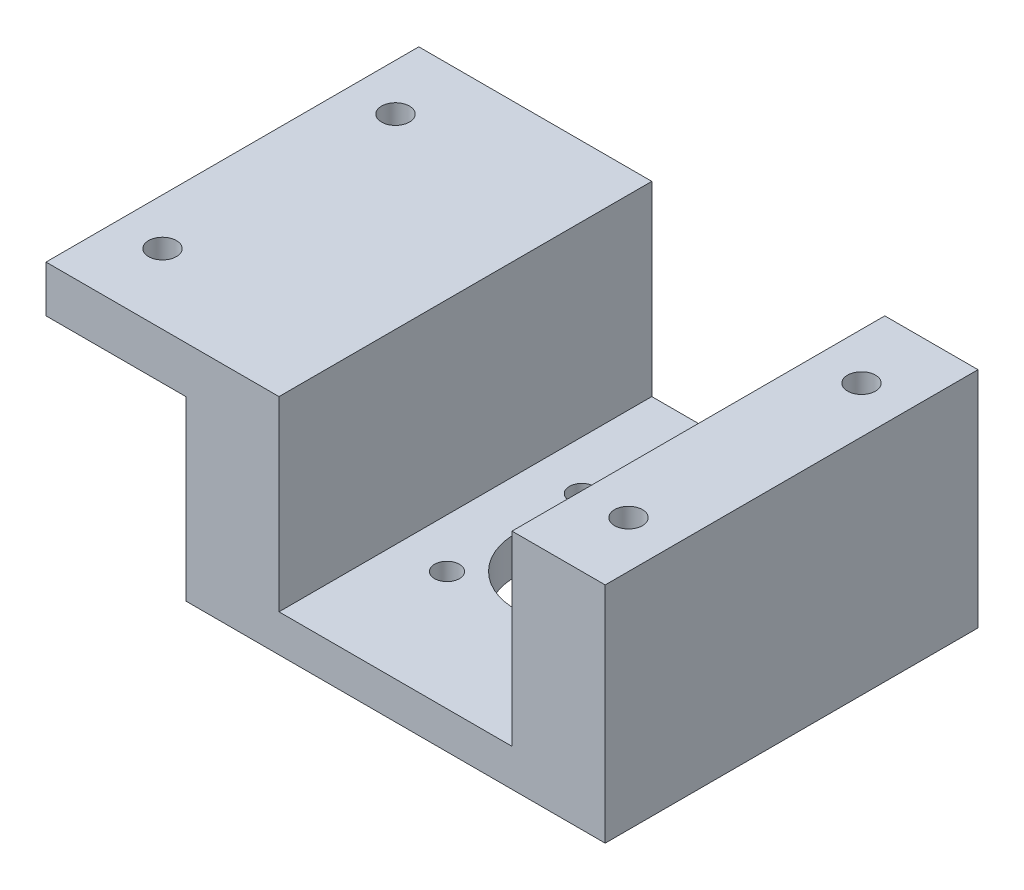
SolidWorks part; units mm, degrees
material "6061 Alloy"
ref_plane "Front Plane" through (0, 0, 0) normal (0, 0, 1) x (1, 0, 0)
ref_plane "Top Plane" through (0, 0, 0) normal (0, 1, 0) x (1, 0, 0)
ref_plane "Right Plane" through (0, 0, 0) normal (1, 0, 0) x (0, 0, -1)
sketch "Sketch1" plane through (0, 0, 0) normal (0, 1, 0) x (1, 0, 0)
  line L1 (-38.1, -25.4) -> (38.1, -25.4)
  line L2 (-38.1, -25.4) -> (-38.1, 25.4)
  line L3 (-38.1, 25.4) -> (38.1, 25.4)
  line L4 (38.1, -25.4) -> (38.1, 25.4)
  line L5 (-38.1, -25.4) -> (38.1, 25.4) construction
  line L6 (-38.1, 25.4) -> (38.1, -25.4) construction
  point P0 (0, 0)
  dimension "D1" = 76.2
  dimension "D2" = 50.8
extrude "Boss-Extrude1" add sketch "Sketch1" along normal blind 30.48
sketch "Sketch2" plane through (0, 0, 0) normal (0, -1, 0) x (1, 0, 0)
  line L0 (-38.1, 0) -> (38.1, 0) construction
  line L1 (-38.1, -25.4) -> (-38.1, 25.4) construction
  line L2 (38.1, 25.4) -> (38.1, -25.4) construction
  line L3 (0, 25.4) -> (0, -25.4) construction
  line L4 (-38.1, 25.4) -> (38.1, 25.4) construction
  line L5 (38.1, -25.4) -> (-38.1, -25.4) construction
  circle A1 centre (9.525, 0) radius 9
  point P12 (-9.525, 0)
  point P13 (9.525, 0)
  dimension "D3" = 18
  dimension "D1" = 19.05
  dimension "D2" = 9.525
extrude "Cut-Extrude1" cut sketch "Sketch2" against normal through all contours A1
sketch "Sketch3" plane through (0, 30.48, 0) normal (0, 1, 0) x (1, 0, 0)
  line L0 (9.525, 0) -> (-9.525, 0) construction
  line L1 (-12.7, -19.05) -> (12.7, -19.05)
  line L2 (-25.4, -6.35) -> (-25.4, 6.35)
  line L3 (-12.7, 19.05) -> (12.7, 19.05)
  line L4 (25.4, -6.35) -> (25.4, 6.35)
  line L5 (-25.4, -19.05) -> (25.4, 19.05) construction
  line L6 (-25.4, 19.05) -> (25.4, -19.05) construction
  arc A0 (12.7, 19.05) -> (25.4, 6.35) centre (12.7, 6.35) cw
  arc A1 (25.4, -6.35) -> (12.7, -19.05) centre (12.7, -6.35) cw
  arc A2 (-12.7, -19.05) -> (-25.4, -6.35) centre (-12.7, -6.35) cw
  arc A3 (-25.4, 6.35) -> (-12.7, 19.05) centre (-12.7, 6.35) cw
  point P0 (0, 0)
  point P9 (0, 0)
  point P22 (-21.87, 0)
  dimension "D3" = 12.7
  dimension "D1" = 38.1
  dimension "D2" = 50.8
  dimension "D4" = 19.05
extrude "Cut-Extrude2" cut sketch "Sketch3" against normal blind 25.4
sketch "Sketch4" plane through (0, 0, 0) normal (0, -1, 0) x (1, 0, 0)
  line L0 (-31.75, 25.4) -> (-31.75, -25.4) construction
  line L1 (-38.1, 25.4) -> (38.1, 25.4) construction
  line L2 (38.1, -25.4) -> (-38.1, -25.4) construction
  line L3 (31.75, 25.4) -> (31.75, -25.4) construction
  line L4 (-38.1, -25.4) -> (-38.1, 25.4) construction
  line L5 (38.1, 25.4) -> (38.1, -25.4) construction
  line L6 (-31.75, 0) -> (31.75, 0) construction
  line L7 (0.3326, 9.1924) -> (18.7174, -9.1924) construction
  line L8 (18.7174, 9.1924) -> (0.3326, -9.1924) construction
  circle A1 centre (9.525, 0) radius 9 construction
  point P12 (-31.75, 15.875)
  point P13 (-31.75, -15.875)
  point P14 (31.75, 15.875)
  point P15 (31.75, -15.875)
  point P20 (9.525, 0)
  point P25 (9.525, 0)
  point P27 (0.3326, 9.1924)
  point P28 (18.7174, 9.1924)
  point P29 (18.7174, -9.1924)
  point P30 (0.3326, -9.1924)
  dimension "D1" = 6.35
  dimension "D2" = 6.35
  dimension "D3" = 31.75
  dimension "D4" = 45
  dimension "D5" = 45
  dimension "D6" = 26
hole_wizard "M3 Clearance Hole1" positions "3DSketch1" profile "Sketch5" hole size "M3" standard "ANSI Metric" end condition through all
sketch3d "3DSketch1"
  point P6 (0.3326, 0, 9.1924)
  point P9 (0.3326, 0, -9.1924)
  point P12 (18.7174, 0, 9.1924)
  point P15 (18.7174, 0, -9.1924)
sketch "Sketch5" plane through (0.3326, 0, 9.1924) normal (1, 0, 0) x (0, 0, -1)
  line L0 (0, 0) -> (0, 30.48)
  line L1 (0, 30.48) -> (1.7, 30.48)
  line L2 (1.7, 30.48) -> (1.7, 0)
  line L5 (1.7, 0) -> (0, 0)
  line L11 (0, -6.35) -> (0, 107.95) construction
  dimension "Thru Hole Dia." = 3.4
  dimension "Thru Hole Depth" = 30.48
hole_wizard "#6 Clearance Hole1" positions "3DSketch2" profile "Sketch6" hole size "#6" standard "ANSI Inch" end condition through all
sketch3d "3DSketch2"
  point P0 (-31.75, 0, 15.875)
  point P3 (-31.75, 0, -15.875)
  point P6 (31.75, 0, 15.875)
  point P9 (31.75, 0, -15.875)
sketch "Sketch6" plane through (-31.75, 0, 15.875) normal (1, 0, 0) x (0, 0, -1)
  line L0 (0, 0) -> (0, 30.48)
  line L1 (0, 30.48) -> (1.8986, 30.48)
  line L2 (1.8986, 30.48) -> (1.8986, 0)
  line L5 (1.8986, 0) -> (0, 0)
  line L11 (0, -6.35) -> (0, 107.95) construction
  dimension "Thru Hole Dia." = 3.7973
  dimension "Thru Hole Depth" = 30.48
sketch "Sketch7" plane through (0, 0, 25.4) normal (0, 0, 1) x (1, 0, 0)
  line L0 (18.525, 5.08) -> (0.525, 5.08) construction
  line L1 (-38.1, 0) -> (-19.05, 0)
  line L2 (-38.1, 0) -> (-38.1, 24.13)
  line L3 (-38.1, 24.13) -> (-19.05, 24.13)
  line L4 (-19.05, 0) -> (-19.05, 24.13)
  line L5 (18.525, 5.08) -> (0.525, 5.08)
  line L6 (9.525, 5.08) -> (9.525, 17.1843) construction
  line L7 (38.1, 30.48) -> (38.1, 0) construction
  line L8 (-38.1, 30.48) -> (38.1, 30.48) construction
  dimension "D1" = 6.35
extrude "Cut-Extrude3" cut sketch "Sketch7" against normal through all contours L2 L1 L4 L3
sketch "Sketch8" plane through (0, 5.08, 0) normal (0, 1, 0) x (1, 0, 0)
  line L0 (-38.1, -25.4) -> (38.1, -25.4) construction
  line L1 (-19.05, -25.4) -> (-6.35, -25.4)
  line L2 (-19.05, -25.4) -> (-19.05, 25.4)
  line L3 (-19.05, 25.4) -> (-6.35, 25.4)
  line L4 (-6.35, -25.4) -> (-6.35, 25.4)
  line L5 (38.1, 25.4) -> (-38.1, 25.4) construction
  line L6 (-19.05, 17.3485) -> (-19.05, -17.3485) construction
  line L7 (9.525, 0) -> (9.525, 15.6606) construction
  line L8 (25.4, -6.35) -> (25.4, 6.35) construction
extrude "Boss-Extrude2" add sketch "Sketch8" along normal up to surface (25.4 mm away) up to face at (-31.75, 30.48, 13.9764)
fillet "Fillet1" radius 12.7 2 edges at (-6.35, 17.78, 19.05) (-6.35, 17.78, -19.05)
sketch "Sketch9" plane through (0, 30.48, 0) normal (0, 1, 0) x (1, 0, 0)
  line L0 (-19.05, -17.3485) -> (-19.05, 17.3485) construction
  line L1 (-25.4, 6.35) -> (-25.4, -6.35) construction
  line L2 (-19.05, -17.3485) -> (-19.05, 17.3485)
  line L3 (-25.4, 6.35) -> (-25.4, -6.35)
  arc A0 (-25.4, -6.35) -> (-19.05, -17.3485) centre (-12.7, -6.35) ccw construction
  arc A1 (-19.05, 17.3485) -> (-25.4, 6.35) centre (-12.7, 6.35) ccw construction
  arc A2 (-25.4, -6.35) -> (-19.05, -17.3485) centre (-12.7, -6.35) ccw
  arc A3 (-19.05, 17.3485) -> (-25.4, 6.35) centre (-12.7, 6.35) ccw
extrude "Boss-Extrude3" add sketch "Sketch9" against normal up to surface (6.35 mm away) up to face at (-31.75, 24.13, -17.7736)
sketch "Sketch10" plane through (0, 0, 25.4) normal (0, 0, 1) x (1, 0, 0)
  line L0 (6.35, 30.48) -> (12.7, 30.48) construction
  line L1 (6.35, 5.08) -> (12.7, 5.08) construction
  line L2 (6.35, 30.48) -> (-6.35, 30.48) construction
  line L3 (25.4, 30.48) -> (12.7, 30.48) construction
  line L4 (25.4, 5.08) -> (25.4, 30.48) construction
  line L5 (25.4, 5.08) -> (12.7, 5.08) construction
  line L6 (6.35, 5.08) -> (-6.35, 5.08) construction
  line L7 (-6.35, 30.48) -> (-6.35, 5.08) construction
  line L8 (6.35, 30.48) -> (12.7, 30.48)
  line L9 (6.35, 5.08) -> (12.7, 5.08)
  line L10 (6.35, 30.48) -> (-6.35, 30.48)
  line L11 (25.4, 30.48) -> (12.7, 30.48)
  line L12 (25.4, 5.08) -> (25.4, 30.48)
  line L13 (25.4, 5.08) -> (12.7, 5.08)
  line L14 (6.35, 5.08) -> (-6.35, 5.08)
  line L15 (-6.35, 30.48) -> (-6.35, 5.08)
extrude "Cut-Extrude4" cut sketch "Sketch10" against normal through all
equation "\"D2@Sketch4\"=\"D1@Sketch4\""
equation "\"D2@Sketch2\"=\"D1@Sketch2\"/2"
